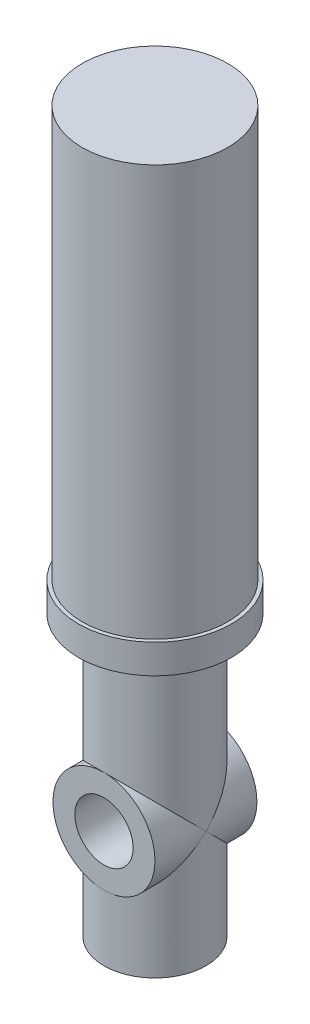
SolidWorks part; units mm, degrees
ref_plane "Front Plane" through (0, 0, 0) normal (0, 0, 1) x (1, 0, 0)
ref_plane "Top Plane" through (0, 0, 0) normal (0, 1, 0) x (1, 0, 0)
ref_plane "Right Plane" through (0, 0, 0) normal (1, 0, 0) x (0, 0, -1)
sketch "Sketch1" plane through (0, 0, 0) normal (0, 1, 0) x (1, 0, 0)
  circle A0 centre (0, 0) radius 35
  dimension "D1" = 70
extrude "Boss-Extrude1" add sketch "Sketch1" along normal blind 132 and the other way blind 80
sketch "Sketch2" plane through (0, 0, 0) normal (0, 0, 1) x (1, 0, 0)
  circle A0 centre (0, 0) radius 35
  dimension "D1" = 70
extrude "Boss-Extrude2" add sketch "Sketch2" along normal blind 35 and the other way blind 35
sketch "Sketch3" plane through (0, 132, 0) normal (0, 1, 0) x (1, 0, 0)
  circle A0 centre (0, 0) radius 52.5
  dimension "D1" = 105
extrude "Boss-Extrude3" add sketch "Sketch3" against normal blind 20
sketch "Sketch4" plane through (0, 132, 0) normal (0, 1, 0) x (1, 0, 0)
  circle A0 centre (0, 0) radius 50
  dimension "D1" = 100
extrude "Boss-Extrude4" add sketch "Sketch4" along normal blind 282
sketch "Sketch5" plane through (0, 0, 35) normal (0, 0, 1) x (1, 0, 0)
  circle A0 centre (0, 0) radius 20
  dimension "D1" = 40
extrude "Cut-Extrude1" cut sketch "Sketch5" against normal through all and the other way through all
